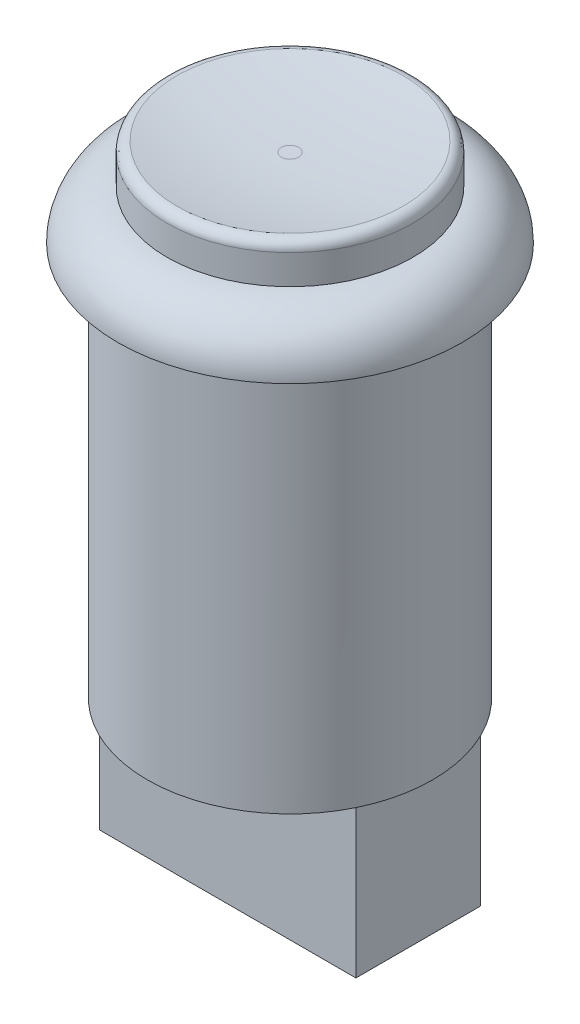
SolidWorks part; units mm, degrees
ref_plane "Front Plane" through (0, 0, 0) normal (0, 0, 1) x (1, 0, 0)
ref_plane "Top Plane" through (0, 0, 0) normal (0, 1, 0) x (1, 0, 0)
ref_plane "Right Plane" through (0, 0, 0) normal (1, 0, 0) x (0, 0, -1)
sketch "Sketch1" plane through (0, 0, 0) normal (0, 1, 0) x (1, 0, 0)
  circle A0 centre (0, 0) radius 17.5
  dimension "D2" = 35
extrude "Boss-Extrude1" add sketch "Sketch1" along normal blind 5
fillet "Fillet1" radius 5 1 edges at (0, 5, 17.5)
sketch "Sketch2" plane through (0, 5, 0) normal (0, 1, 0) x (1, 0, 0)
  circle A0 centre (0, 0) radius 12.5 construction
  circle A1 centre (0, 0) radius 12.5
extrude "Boss-Extrude2" add sketch "Sketch2" along normal blind 4
fillet "Fillet2" radius 1 1 edges at (0, 9, 12.5)
sketch "Sketch3" plane through (0, 9, 0) normal (0, 1, 0) x (1, 0, 0)
  circle A0 centre (0, 0) radius 11.5 construction
  circle A1 centre (0, 0) radius 11.5
extrude "Cut-Extrude1" cut sketch "Sketch3" against normal blind 1 contours A1
fillet "Fillet5" radius 57 1 edges at (0, 8, 11.5)
sketch "Sketch5" plane through (0, 0, 0) normal (0, -1, 0) x (1, 0, 0)
  circle A2 centre (0, 0) radius 14.5
  circle A3 centre (0, 0) radius 14.5
  dimension "D1" = 3
extrude "Boss-Extrude3" add sketch "Sketch5" along normal blind 40
sketch "Sketch6" plane through (0, -40, 0) normal (0, -1, 0) x (1, 0, 0)
  line L1 (-13.041, -6.339) -> (13.041, -6.339)
  line L2 (-13.041, -6.339) -> (-13.041, 6.339)
  line L3 (-13.041, 6.339) -> (13.041, 6.339)
  line L4 (13.041, -6.339) -> (13.041, 6.339)
  line L5 (-13.041, -6.339) -> (13.041, 6.339) construction
  line L6 (-13.041, 6.339) -> (13.041, -6.339) construction
  circle A0 centre (0, 0) radius 14.5 construction
  point P0 (0, 0)
extrude "Boss-Extrude4" add sketch "Sketch6" along normal blind 15
